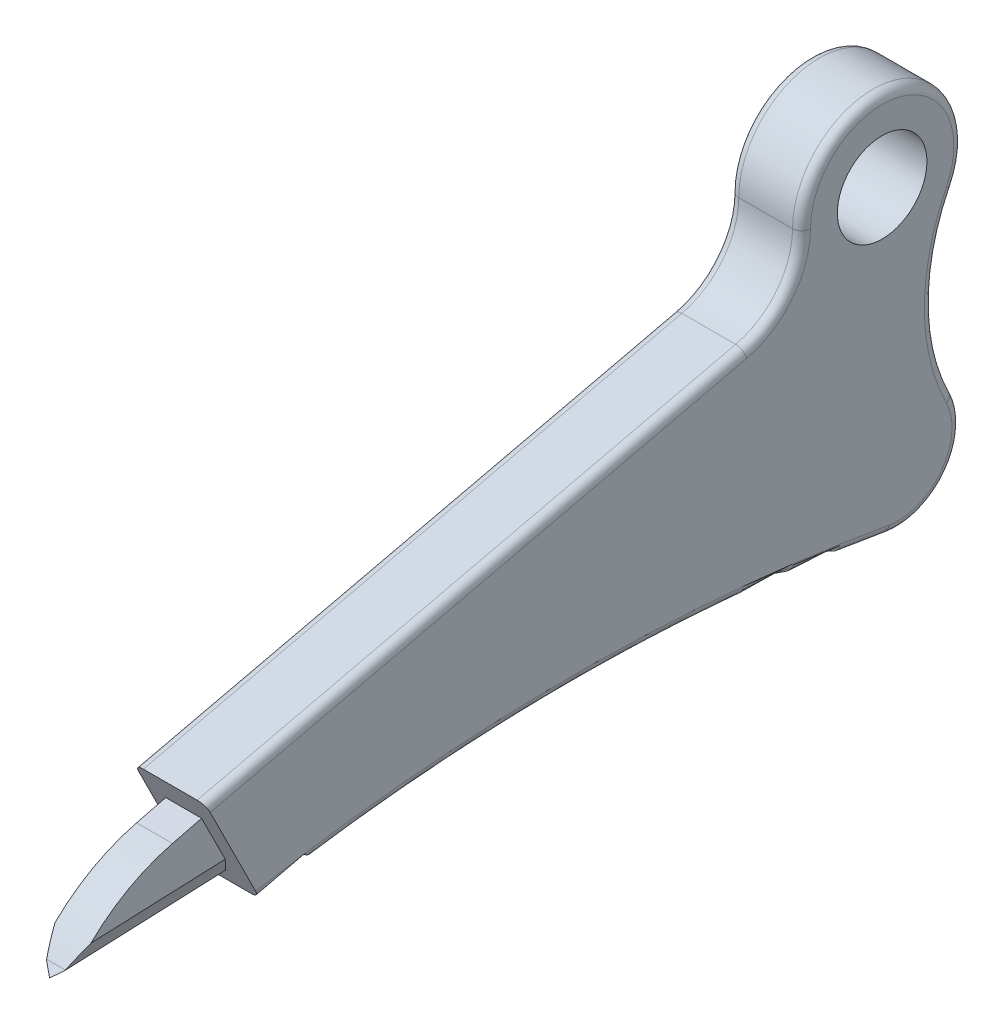
SolidWorks part; units mm, degrees
ref_plane "Front Plane" through (0, 0, 0) normal (0, 0, 1) x (1, 0, 0)
ref_plane "Top Plane" through (0, 0, 0) normal (0, 1, 0) x (1, 0, 0)
ref_plane "Right Plane" through (0, 0, 0) normal (1, 0, 0) x (0, 0, -1)
sketch "Sketch1" plane through (0, 0, 0) normal (1, 0, 0) x (0, 0, -1)
  line L0 (-88.1775, -43.18) -> (-95.7975, -27.94)
  line L1 (-95.7975, -27.94) -> (-19.4947, -10.16)
  circle A0 centre (0, 0) radius 6.35
  arc A1 (-11.43, 0) -> (10.2391, -5.08) centre (0, 0) cw
  arc A2 (10.2391, -5.08) -> (10.2391, -30.48) centre (35.8367, -17.78) ccw
  arc A3 (10.2391, -30.48) -> (0.7225, -43.18) centre (2.2778, -34.4299) cw
  arc A4 (0.7225, -43.18) -> (-88.1775, -43.18) centre (-43.7275, -293.2604) ccw
  arc A5 (-19.4947, -10.16) -> (-11.43, 0) centre (-21.8622, 0) ccw
  dimension "D1" = 12.7
  dimension "D2" = 11.43
  dimension "D11" = 254
  dimension "D3" = 5.08
  dimension "D4" = 25.4
  dimension "D5" = 12.7
  dimension "D6" = 88.9
  dimension "D7" = 7.62
  dimension "D8" = 15.24
  dimension "D10" = 10.16
extrude "Boss-Extrude1" add sketch "Sketch1" along normal mid plane 10.16
fillet "Fillet1" radius 1.27 12 edges at (-5.08, -39.2604, 43.7275) (-5.08, -39.7592, -9.3899) (-5.08, -17.78, -7.2617) (-5.08, 11.1283, -2.6089) (-5.08, -6.4859, 13.6912) (5.08, -39.2604, 43.7275) (5.08, -39.7592, -9.3899) (5.08, -17.78, -7.2617) (5.08, 11.1283, -2.6089) (5.08, -6.4859, 13.6912) (-5.08, -19.05, 57.6461) (5.08, -19.05, 57.6461)
sketch "Sketch3" plane through (0, 0, 0) normal (1, 0, 0) x (0, 0, -1)
  line L0 (-93.8925, -31.75) -> (-106.5925, -34.925)
  line L1 (-95.2135, -29.1079) -> (-88.7696, -41.9956) construction
  line L2 (-106.5925, -34.925) -> (-112.9425, -43.18)
  line L3 (-112.9425, -43.18) -> (-92.6225, -42.3397)
  line L4 (-92.6225, -42.3397) -> (-43.9154, -37.9905)
  line L5 (-43.9154, -37.9905) -> (-93.8925, -31.75)
  arc A0 (0.9448, -41.9296) -> (-88.7696, -41.9956) centre (-43.7275, -293.2604) ccw construction
  dimension "D1" = 20.32
  dimension "D2" = 3.81
  dimension "D3" = 12.7
  dimension "D4" = 3.175
  dimension "D5" = 6.35
extrude "Boss-Extrude2" add sketch "Sketch3" along normal mid plane 5.08
chamfer "Chamfer1" distance 3.81 angle 25 2 edges at (-2.54, -42.7598, 102.7825) (2.54, -42.7598, 102.7825) first distance on face at (-2.54, -38.8381, 98.9639) first distance on face at (2.54, -38.8381, 98.9639)
fillet "Fillet2" radius 25.4 1 edges at (0, -34.925, 106.5925)
chamfer "Chamfer2" distance 1.27 angle 25 2 edges at (-0.7634, -42.7598, 102.7825) (0.7634, -42.7598, 102.7825) first distance on face at (-1.467, -41.1792, 101.0818) first distance on face at (1.467, -41.1792, 101.0818)
